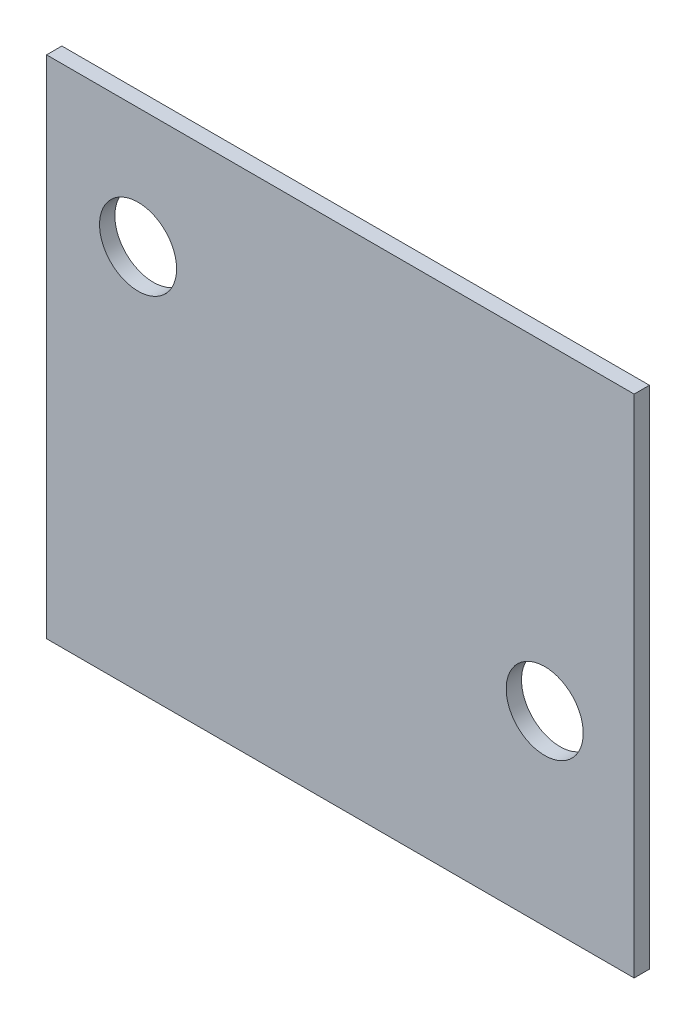
SolidWorks part; units mm, degrees
material "6061-T6 (SS)"
ref_plane "Front" through (0, 0, 0) normal (0, 0, 1) x (1, 0, 0)
ref_plane "Top" through (0, 0, 0) normal (0, 1, 0) x (1, 0, 0)
ref_plane "Right" through (0, 0, 0) normal (1, 0, 0) x (0, 0, -1)
ref_axis "side-side" through (80.9, 0, 0) along (-1, 0, 0)
ref_axis "up-down" through (0, 50, 0) along (0, -1, 0)
ref_axis "front-back" through (0, 0, -80.9) along (0, 0, 1)
sketch "Sketch1" plane through (0, 0, 0) normal (0, 0, 1) x (1, 0, 0)
  line L1 (103, -80) -> (-19, -80)
  line L2 (103, -80) -> (103, 25)
  line L3 (103, 25) -> (-19, 25)
  line L4 (-19, -80) -> (-19, 25)
  circle A1 centre (84.4311, -41.275) radius 8
  circle A2 centre (0, 0) radius 8 construction
  circle A3 centre (0, 0) radius 8
  circle A4 centre (84.4311, -41.275) radius 4 construction
  point P10 (-18, -72.5621)
  point P11 (0, 0)
  point P13 (0, 0)
  dimension "D4" = 25
  dimension "D1" = 122
  dimension "D2" = 19
  dimension "D3" = 80
extrude "Boss-Extrude1" add sketch "Sketch1" against normal blind 3.175
